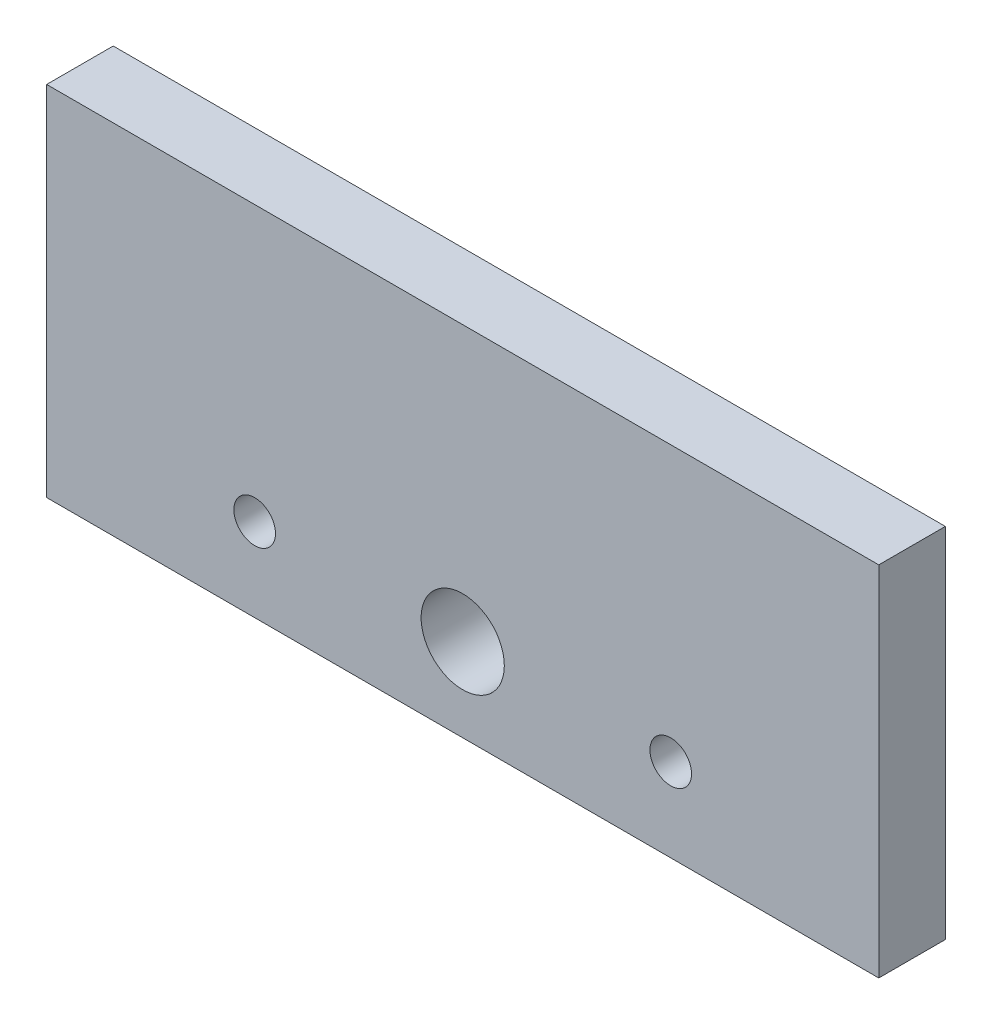
SolidWorks part; units mm, degrees
ref_plane "前视基准面" through (0, 0, 0) normal (0, 0, 1) x (1, 0, 0)
ref_plane "上视基准面" through (0, 0, 0) normal (0, 1, 0) x (1, 0, 0)
ref_plane "右视基准面" through (0, 0, 0) normal (1, 0, 0) x (0, 0, -1)
sketch "草图2" plane through (0, 0, 0) normal (0, 0, 1) x (1, 0, 0)
  line L1 (0, 0) -> (100, 0)
  line L2 (0, 0) -> (0, 43)
  line L3 (0, 43) -> (100, 43)
  line L4 (100, 0) -> (100, 43)
  dimension "D1" = 43
  dimension "D2" = 100
extrude "凸台-拉伸1" add sketch "草图2" along normal blind 8
sketch "草图3" plane through (0, 0, 8) normal (0, 0, 1) x (1, 0, 0)
  line L0 (50, 43) -> (50, 0) construction
  line L1 (100, 43) -> (0, 43) construction
  line L2 (0, 0) -> (100, 0) construction
  circle A0 centre (50, 10) radius 5
  dimension "D1" = 10
  dimension "D2" = 10
extrude "切除-拉伸1" cut sketch "草图3" against normal blind 8
hole_wizard "M6 螺纹孔1" positions "草图5" profile "草图6" tap size "M6" standard "ISO"
sketch "草图5" plane through (0, 0, 8) normal (0, 0, 1) x (1, 0, 0)
  line L0 (50, 43) -> (50, -5.0175) construction
  line L1 (100, 43) -> (0, 43) construction
  line L3 (0, 0) -> (100, 0) construction
  circle A0 centre (50, 10) radius 5 construction
  point P0 (25, 10)
  point P9 (75, 10)
  dimension "D1" = 25
  dimension "D2" = 10
sketch "草图6" plane through (25, 10, 8) normal (1, 0, 0) x (0, -1, 0)
  line L0 (0, 0) -> (0, 16.5022)
  line L1 (0, 16.5022) -> (2.5, 15)
  line L2 (2.5, 15) -> (2.5, 0)
  line L5 (2.5, 0) -> (0, 0)
  line L10 (0, 16.5022) -> (-2.5, 15) construction
  line L11 (0, -6.35) -> (0, 107.95) construction
  dimension "螺纹孔钻头直径" = 5
  dimension "螺纹孔钻头深度" = 15
  dimension "导头角度" = 118
cosmetic thread "孔螺蚊线1" parameters "D1"=8, "D2"=6
cosmetic thread "孔螺蚊线2" parameters "D1"=8, "D2"=6
